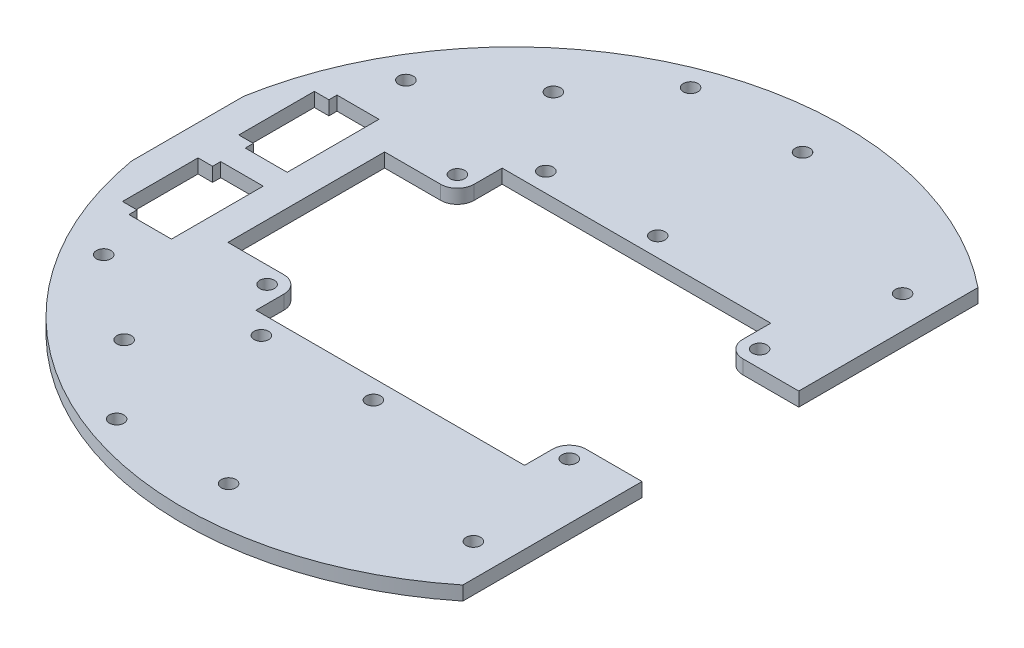
SolidWorks part; units mm, degrees
material "Acrylic (Medium-high impact)"
ref_plane "Front Plane" through (0, 0, 0) normal (0, 0, 1) x (1, 0, 0)
ref_plane "Top Plane" through (0, 0, 0) normal (0, 1, 0) x (1, 0, 0)
ref_plane "Right Plane" through (0, 0, 0) normal (1, 0, 0) x (0, 0, -1)
sketch "Sketch1" plane through (0, 0, 0) normal (0, 1, 0) x (1, 0, 0)
  line L0 (-73.9169, 12.7) -> (-73.9169, -12.7)
  line L1 (-46.99, 0) -> (-73.9169, 0) construction
  line L2 (-34.29, 21.59) -> (34.29, 21.59) construction
  line L3 (34.29, 21.59) -> (34.29, -21.59) construction
  line L4 (34.29, -21.59) -> (-34.29, -21.59) construction
  line L5 (-34.29, -21.59) -> (-34.29, 21.59) construction
  line L6 (0, 21.59) -> (0, 75) construction
  line L7 (34.29, 0) -> (75, 0) construction
  line L8 (0, -25.4) -> (0, -21.59) construction
  line L9 (-34.29, 0) -> (-38.1, 0) construction
  line L10 (-30.48, 27.94) -> (30.48, 27.94)
  line L11 (-30.48, 27.94) -> (-30.48, 21.59)
  line L12 (0, 21.59) -> (0, 27.94) construction
  line L13 (30.48, 27.94) -> (30.48, 21.59)
  line L14 (34.29, 17.78) -> (46.99, 17.78)
  line L15 (-73.9169, 12.7) -> (-73.9169, -12.7) construction
  line L16 (34.29, -17.78) -> (46.99, -17.78)
  line L17 (46.99, 17.78) -> (46.99, -17.78)
  line L18 (-66.9971, -4.5609) -> (-63.6951, -4.5609)
  line L19 (30.48, -21.59) -> (30.48, -27.94)
  line L20 (30.48, -27.94) -> (-30.48, -27.94)
  line L21 (-30.48, -21.59) -> (-30.48, -27.94)
  line L22 (-46.99, -17.78) -> (-34.29, -17.78)
  line L23 (-46.99, -17.78) -> (-46.99, 17.78)
  line L24 (-46.99, 17.78) -> (-34.29, 17.78)
  line L25 (-66.9971, -4.5609) -> (-66.9971, -21.7059)
  line L26 (-66.9971, -21.7059) -> (-63.6951, -21.7059)
  line L27 (-54.04, -4.559) -> (-54.04, -21.7077)
  line L28 (-36.4519, -35.4485) -> (12.0481, -35.4485) construction
  line L29 (12.0481, -35.4485) -> (12.0481, -61.9485) construction
  line L30 (-24.9019, -35.4485) -> (-24.9019, -32.2735) construction
  line L31 (12.0481, -61.9485) -> (-36.4519, -61.9485) construction
  line L32 (-36.4519, -61.9485) -> (-36.4519, -35.4485) construction
  line L35 (-36.4519, -35.4485) -> (-36.4519, -27.94) construction
  line L36 (-12.2019, -35.4485) -> (-12.2019, -61.9485) construction
  line L37 (-63.6951, -4.5609) -> (-63.6951, -2.7212)
  line L38 (-39.6269, -48.6985) -> (-36.4519, -48.6985) construction
  line L39 (-24.9019, -65.1235) -> (-24.9019, -61.9485) construction
  line L40 (-66.867, 21.7077) -> (-63.565, 21.7077)
  line L41 (-66.867, 21.7077) -> (-66.867, 4.5627)
  line L42 (-66.867, 4.5627) -> (-63.565, 4.5627)
  line L43 (-54.04, 21.7077) -> (-54.04, 4.5627)
  line L44 (-63.565, 21.7077) -> (-63.565, 23.5492)
  line L45 (-63.565, 23.5492) -> (-54.04, 23.5492)
  line L46 (-54.04, 23.5492) -> (-54.04, 21.7077)
  line L47 (-63.565, 4.5627) -> (-63.565, 2.7212)
  line L48 (-63.565, 2.7212) -> (-54.04, 2.7212)
  line L49 (-54.04, 2.7212) -> (-54.04, 4.5627)
  line L50 (-63.6951, -2.7212) -> (-54.04, -2.7212)
  line L51 (55.1757, 50.8) -> (55.1757, -50.8) construction
  line L52 (-54.04, -2.7212) -> (-54.04, -4.559)
  line L53 (-63.6951, -21.7059) -> (-63.6951, -23.5455)
  line L54 (-63.6951, -23.5455) -> (-54.04, -23.5455)
  line L55 (-54.04, -23.5455) -> (-54.04, -21.7077)
  line L56 (-54.04, 2.7212) -> (-54.04, -2.7212) construction
  line L57 (-73.9169, 0) -> (-54.04, 0) construction
  arc A0 (-73.9169, -12.7) -> (-73.9169, 12.7) centre (0, 0) ccw
  arc A1 (55.356, -50.6035) -> (55.356, 50.6035) centre (0, 0) ccw construction
  circle A2 centre (-34.29, 21.59) radius 1.651
  circle A3 centre (34.29, 21.59) radius 1.651
  circle A4 centre (-34.29, -21.59) radius 1.651
  circle A5 centre (34.29, -21.59) radius 1.651
  circle A6 centre (-39.6269, 48.6985) radius 1.651 construction
  circle A7 centre (39.6269, -48.6985) radius 1.651
  circle A9 centre (-58.6769, -34.29) radius 1.651
  circle A10 centre (-58.6769, 34.29) radius 1.651
  circle A12 centre (39.6269, 48.6985) radius 1.651
  circle A13 centre (39.6269, -48.6985) radius 1.651 construction
  circle A14 centre (0.4981, -65.1235) radius 1.651
  circle A15 centre (0.4981, -32.2735) radius 1.651
  circle A16 centre (0.4981, 32.2735) radius 1.651
  circle A17 centre (0.4981, 65.1235) radius 1.651
  arc A18 (-34.29, 17.78) -> (-30.48, 21.59) centre (-34.29, 21.59) ccw
  arc A19 (-34.29, -17.78) -> (-30.48, -21.59) centre (-34.29, -21.59) cw
  arc A20 (30.48, 21.59) -> (34.29, 17.78) centre (34.29, 21.59) ccw
  arc A21 (30.48, -21.59) -> (34.29, -17.78) centre (34.29, -21.59) cw
  circle A22 centre (-39.6269, -48.6985) radius 1.651
  circle A23 centre (-24.9019, -32.2735) radius 1.651
  circle A24 centre (-24.9019, -65.1235) radius 1.651
  circle A25 centre (-24.9019, 65.1235) radius 1.651
  circle A26 centre (-39.6269, 48.6985) radius 1.651
  circle A27 centre (-24.9019, 32.2735) radius 1.651
  dimension "D11" = 3.302
  dimension "D1" = 68.58
  dimension "D2" = 43.18
  dimension "D3" = 3.81
  dimension "D4" = 12.7
  dimension "D5" = 60.96
  dimension "D6" = 35.56
  dimension "D7" = 48.5
  dimension "D8" = 26.5
  dimension "D9" = 12.7
  dimension "D10" = 3.175
  dimension "D12" = 17.145
  dimension "D13" = 6.35
  dimension "D14" = 101.6
  dimension "D15" = 3.302
  dimension "D16" = 20.828
  dimension "D17" = 9.525
  dimension "D18" = 1.8415
  dimension "D19" = 1.8377
  dimension "D20" = 17.145
  dimension "D21" = 3.302
  dimension "D22" = 9.6551
  dimension "D23" = 20.8242
extrude "Boss-Extrude1" add sketch "Sketch1" along normal blind 3.175
sketch "Sketch2" plane through (0, 3.175, 0) normal (0, 1, 0) x (1, 0, 0)
  line L1 (46.99, -17.78) -> (46.99, 17.78) construction
  line L6 (46.99, 58.4546) -> (46.99, -58.4546)
  arc A0 (-73.9169, -12.7) -> (-73.9169, 12.7) centre (0, 0) ccw construction
  arc A1 (46.99, 58.4546) -> (46.99, -58.4546) centre (0, 0) cw
extrude "Cut-Extrude1" cut sketch "Sketch2" against normal up to surface (3.175 mm away) up to face at (-24.9019, 0, -33.9245)
